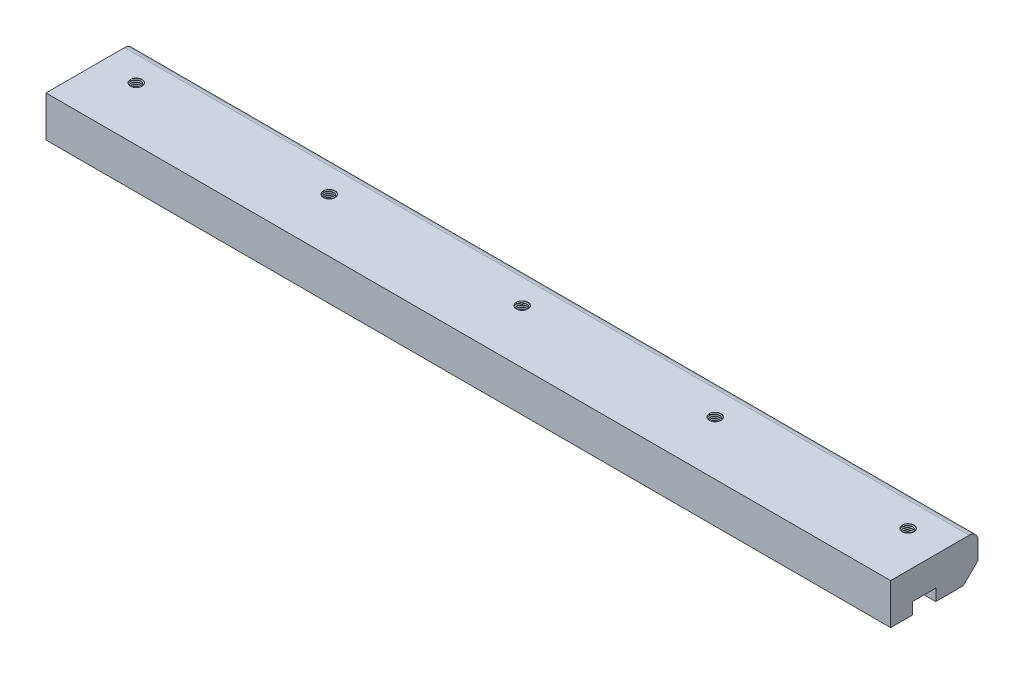
SolidWorks part; units mm, degrees
ref_plane "Alzado" through (0, 0, 0) normal (0, 0, 1) x (1, 0, 0)
ref_plane "Planta" through (0, 0, 0) normal (0, 1, 0) x (1, 0, 0)
ref_plane "Vista lateral" through (0, 0, 0) normal (1, 0, 0) x (0, 0, -1)
sketch "Croquis1" plane through (0, 0, 0) normal (1, 0, 0) x (0, 0, -1)
  line L0 (0, 0) -> (15, 0)
  line L1 (15, 0) -> (15, 8)
  line L2 (15, 8) -> (31, 8)
  line L3 (31, 8) -> (31, 0)
  line L4 (31, 0) -> (50, 0)
  line L5 (50, 0) -> (60, 10)
  line L6 (60, 10) -> (60, 22)
  line L7 (54, 28) -> (0, 28)
  line L8 (0, 28) -> (0, 0)
  line L9 (60, 10) -> (60, 0) construction
  line L10 (60, 0) -> (50, 0) construction
  arc A0 (60, 22) -> (54, 28) centre (54, 22) ccw
  point P13 (60, 28)
  dimension "D8" = 6
  dimension "D1" = 28
  dimension "D2" = 60
  dimension "D3" = 8
  dimension "D4" = 15
  dimension "D5" = 16
  dimension "D6" = 10
  dimension "D7" = 45
extrude "Saliente-Extruir1" add sketch "Croquis1" along normal blind 580
sketch "Croquis2" plane through (0, 28, 0) normal (0, 1, 0) x (1, 0, 0)
  line L0 (0, 54) -> (0, 0) construction
  line L1 (580, 60) -> (0, 60) construction
  line L2 (25, 37) -> (157.5, 37) construction
  circle A0 centre (25, 37) radius 4.0268
  circle A1 centre (157.5, 37) radius 4.0268
  circle A2 centre (290, 37) radius 4.0268
  circle A3 centre (422.5, 37) radius 4.0268
  circle A4 centre (555, 37) radius 4.0268
  dimension "D1" = 25
  dimension "D2" = 23
  dimension "D4" = 132.5
  dimension "D3" = 5
extrude "Cortar-Extruir1" cut sketch "Croquis2" against normal blind 10
thread "Rosca1" pitch 1.25 method extrude profile "Perfil de rosca1" start angle 0, offset 0, length 10, pitch 1.25, diameter 8.0535
ref_plane "Plano1" through (550.9732, 28, -37) normal (0, 0, 1) x (-1, 0, 0)
sketch "Perfil de rosca1" plane through (550.9732, 28, -37) normal (0, 0, 1) x (-1, 0, 0)
  line L0 (0, 0) -> (0, 1.25) construction
  line L11 (0, 0) -> (0, 1.0937)
  line L12 (0, 1.0937) -> (-0.6766, 0.7031)
  line L13 (-0.6766, 0.7031) -> (-0.6766, 0.3906)
  line L15 (-0.6766, 0.3906) -> (0, 0)
  line L17 (-0.6766, 0.5469) -> (0, 0.5469) construction
  point P2 (0, 0)
  dimension "Pitch" = 1.25
  dimension "Profile_Angle" = 60
  dimension "Profile_Land" = 0.3125
  dimension "Profile_Height" = 0.6766
thread "Rosca2" pitch 1.25 method extrude profile "Perfil de rosca2" start angle 0, offset 0, length 10, pitch 1.25, diameter 8.0535
ref_plane "Plano2" through (418.4732, 28, -37) normal (0, 0, 1) x (-1, 0, 0)
sketch "Perfil de rosca2" plane through (418.4732, 28, -37) normal (0, 0, 1) x (-1, 0, 0)
  line L0 (0, 0) -> (0, 1.25) construction
  line L11 (0, 0) -> (0, 1.0937)
  line L12 (0, 1.0937) -> (-0.6766, 0.7031)
  line L13 (-0.6766, 0.7031) -> (-0.6766, 0.3906)
  line L15 (-0.6766, 0.3906) -> (0, 0)
  line L17 (-0.6766, 0.5469) -> (0, 0.5469) construction
  point P2 (0, 0)
  dimension "Pitch" = 1.25
  dimension "Profile_Angle" = 60
  dimension "Profile_Land" = 0.3125
  dimension "Profile_Height" = 0.6766
thread "Rosca3" pitch 1.25 method extrude profile "Perfil de rosca3" start angle 0, offset 0, length 10, pitch 1.25, diameter 8.0535
ref_plane "Plano3" through (285.9732, 28, -37) normal (0, 0, 1) x (-1, 0, 0)
sketch "Perfil de rosca3" plane through (285.9732, 28, -37) normal (0, 0, 1) x (-1, 0, 0)
  line L0 (0, 0) -> (0, 1.25) construction
  line L11 (0, 0) -> (0, 1.0937)
  line L12 (0, 1.0937) -> (-0.6766, 0.7031)
  line L13 (-0.6766, 0.7031) -> (-0.6766, 0.3906)
  line L15 (-0.6766, 0.3906) -> (0, 0)
  line L17 (-0.6766, 0.5469) -> (0, 0.5469) construction
  point P2 (0, 0)
  dimension "Pitch" = 1.25
  dimension "Profile_Angle" = 60
  dimension "Profile_Land" = 0.3125
  dimension "Profile_Height" = 0.6766
thread "Rosca4" pitch 1.25 method extrude profile "Perfil de rosca4" start angle 0, offset 0, length 10, pitch 1.25, diameter 8.0535
ref_plane "Plano4" through (153.4732, 28, -37) normal (0, 0, 1) x (-1, 0, 0)
sketch "Perfil de rosca4" plane through (153.4732, 28, -37) normal (0, 0, 1) x (-1, 0, 0)
  line L0 (0, 0) -> (0, 1.25) construction
  line L11 (0, 0) -> (0, 1.0937)
  line L12 (0, 1.0937) -> (-0.6766, 0.7031)
  line L13 (-0.6766, 0.7031) -> (-0.6766, 0.3906)
  line L15 (-0.6766, 0.3906) -> (0, 0)
  line L17 (-0.6766, 0.5469) -> (0, 0.5469) construction
  point P2 (0, 0)
  dimension "Pitch" = 1.25
  dimension "Profile_Angle" = 60
  dimension "Profile_Land" = 0.3125
  dimension "Profile_Height" = 0.6766
thread "Rosca5" pitch 1.25 profile "Perfil de rosca5" start angle 0, offset 0, length 10, pitch 1.25, diameter 8.0535
ref_plane "Plano5" through (20.9732, 28, -37) normal (0, 0, 1) x (-1, 0, 0)
sketch "Perfil de rosca5" plane through (20.9732, 28, -37) normal (0, 0, 1) x (-1, 0, 0)
  line L0 (0, 0) -> (0, 1.25) construction
  line L11 (0, 0) -> (0, 1.0937)
  line L12 (0, 1.0937) -> (-0.6766, 0.7031)
  line L13 (-0.6766, 0.7031) -> (-0.6766, 0.3906)
  line L15 (-0.6766, 0.3906) -> (0, 0)
  line L17 (-0.6766, 0.5469) -> (0, 0.5469) construction
  point P2 (0, 0)
  dimension "Pitch" = 1.25
  dimension "Profile_Angle" = 60
  dimension "Profile_Land" = 0.3125
  dimension "Profile_Height" = 0.6766
